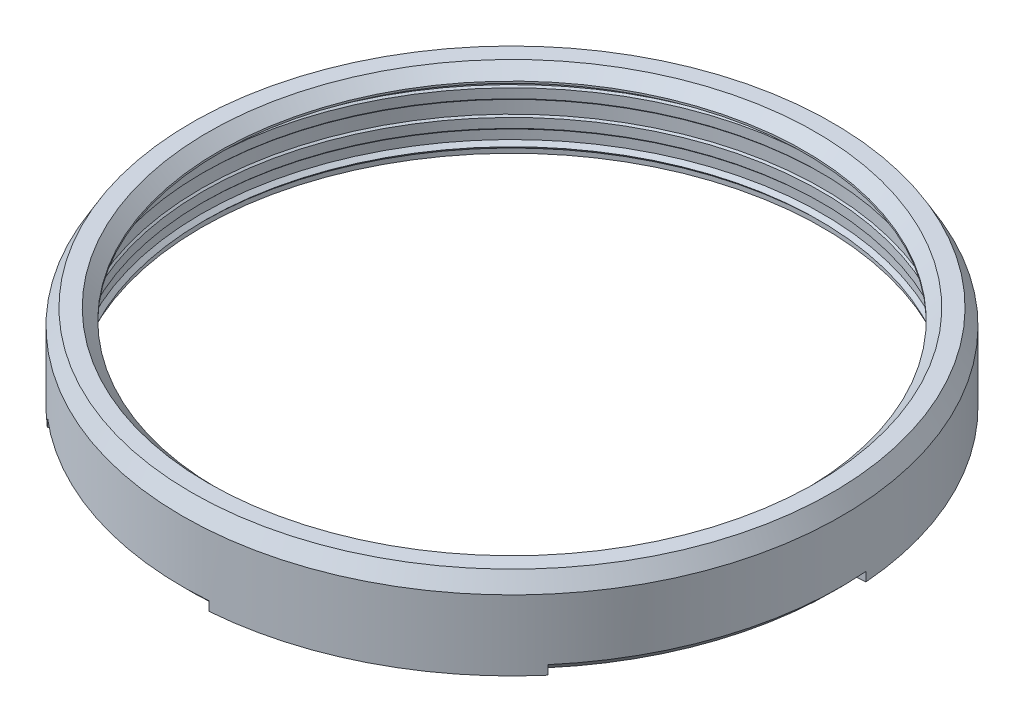
SolidWorks part; units mm, degrees
ref_plane "前视基准面" through (0, 0, 0) normal (0, 0, 1) x (1, 0, 0)
ref_plane "上视基准面" through (0, 0, 0) normal (0, 1, 0) x (1, 0, 0)
ref_plane "右视基准面" through (0, 0, 0) normal (1, 0, 0) x (0, 0, -1)
sketch "草图1" plane through (0, 0, 0) normal (0, 1, 0) x (1, 0, 0)
  circle A0 centre (0, 0) radius 36
  dimension "D1" = 72
extrude "凸台-拉伸1" add sketch "草图1" along normal blind 2.4
sketch "草图2" plane through (0, 0, 0) normal (0, 0, 1) x (1, 0, 0)
  line L0 (33.8, -8) -> (33.8, -7.5) construction
  line L1 (33.8, -7.5) -> (33.4, -7.1) construction
  line L3 (33.4, -7.1) -> (33.8, -6.7) construction
  line L5 (33.8, -6.7) -> (33.8, -5.7) construction
  line L22 (33.8, -5.7) -> (33.62, -5.52) construction
  line L23 (33.62, -5.52) -> (33.62, -4.48) construction
  line L24 (33.62, -4.48) -> (33.8, -4.3) construction
  line L25 (33.8, -4.3) -> (33.8, -2.9) construction
  line L27 (33.8, -2.9) -> (33.62, -2.72) construction
  line L28 (33.62, -2.72) -> (33.62, -1.68) construction
  line L29 (33.62, -1.68) -> (33.8, -1.5) construction
  line L30 (33.8, -8) -> (33.8, -7.5) construction
  line L31 (33.8, -7.5) -> (33.4, -7.1) construction
  line L32 (33.4, -7.1) -> (33.8, -6.7) construction
  line L33 (33.8, -6.7) -> (33.8, -5.7) construction
  line L34 (33.8, -5.7) -> (33.62, -5.52) construction
  line L35 (33.62, -5.52) -> (33.62, -4.48) construction
  line L36 (0, -23.4) -> (0, 16.7887) construction
  line L37 (33.62, -4.48) -> (33.8, -4.3) construction
  line L38 (33.8, -4.3) -> (33.8, -2.9) construction
  line L39 (33.8, -2.9) -> (33.62, -2.72) construction
  line L40 (33.62, -2.72) -> (33.62, -1.68) construction
  line L41 (33.62, -1.68) -> (33.8, -1.5) construction
  line L42 (33.94, -8) -> (33.94, -7.5)
  line L43 (33.94, -7.5) -> (33.54, -7.1)
  line L44 (33.54, -7.1) -> (33.94, -6.7)
  line L45 (33.94, -6.7) -> (33.94, -5.7)
  line L46 (33.94, -5.7) -> (33.76, -5.52)
  line L47 (33.76, -5.52) -> (33.76, -4.48)
  line L48 (33.76, -4.48) -> (33.94, -4.3)
  line L49 (33.94, -4.3) -> (33.94, -2.9)
  line L50 (33.94, -2.9) -> (33.76, -2.72)
  line L51 (33.76, -2.72) -> (33.76, -1.68)
  line L52 (33.76, -1.68) -> (33.94, -1.5)
  line L53 (32.44, 0) -> (36, 0)
  line L54 (36, 0) -> (36, -8)
  line L55 (36, -8) -> (33.94, -8)
  arc A0 (33.8, -1.5) -> (32.3, 0) centre (32.3, -1.5) ccw construction
  arc A1 (33.8, -1.5) -> (32.3, 0) centre (32.3, -1.5) ccw construction
  arc A2 (33.94, -1.5) -> (32.44, 0) centre (32.44, -1.5) ccw
  dimension "D1" = 2
revolve "旋转1" add sketch "草图2" angle 360 about L36 region at (34.894, -3.9175, 0)
sketch "草图3" plane through (0, 2.4, 0) normal (0, 1, 0) x (1, 0, 0)
  circle A0 centre (0, 0) radius 32
  circle A1 centre (0, 0) radius 36 construction
  dimension "D1" = 4
extrude "切除-拉伸1" cut sketch "草图3" against normal blind 10
sketch "草图4" plane through (0, 2.4, 0) normal (0, 1, 0) x (1, 0, 0)
  circle A1 centre (0, 0) radius 36
  circle A2 centre (0, 0) radius 36
  dimension "D1" = 0
extrude "切除-拉伸2" cut sketch "草图4" against normal blind 1
chamfer "倒角3" distance 1.732 angle 30 1 edges at (0, 1.4, 36) first distance on face at (36, -8, 0)
chamfer "倒角2" distance 1.2 angle 45 1 edges at (0, 1.4, 32)
sketch "草图6" plane through (0, 0, 0) normal (0.0772, 0, 0.997) x (0.997, 0, -0.0772)
  line L0 (-35, -8) -> (-36, -7)
  line L1 (-36, -8) -> (36, -8) construction
  line L2 (-35, -8) -> (-35, -20.4) construction
  line L3 (-36, -7) -> (-36, -8)
  line L4 (-36, -8) -> (-35, -8)
  line L5 (0, -23.4) -> (0, -1.7781) construction
revolve "切除-旋转1" cut sketch "草图6" angle 45 about L5 reverse direction yes
pattern_circular "阵列(圆周)1" count 4 every 90 about axis through (0, -23.4, 0) along (0, 1, 0) of "切除-旋转1"
